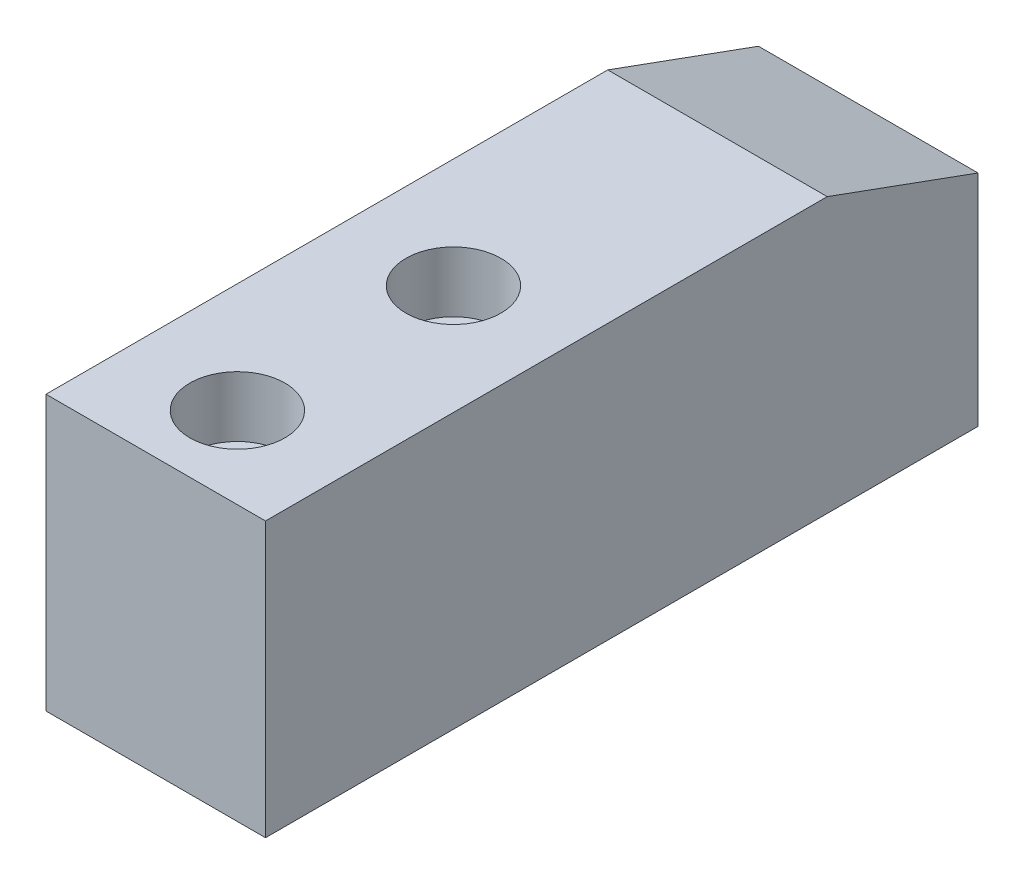
SolidWorks part; units mm, degrees
material "Low Carbon Steel"
ref_plane "Front Plane" through (0, 0, 0) normal (0, 0, 1) x (1, 0, 0)
ref_plane "Top Plane" through (0, 0, 0) normal (0, 1, 0) x (1, 0, 0)
ref_plane "Right Plane" through (0, 0, 0) normal (1, 0, 0) x (0, 0, -1)
sketch "Sketch1" plane through (0, 0, 0) normal (1, 0, 0) x (0, 0, -1)
  line L0 (0, 0) -> (82.4465, 0)
  line L1 (82.4465, 0) -> (82.4465, 25.4)
  line L2 (82.4465, 25.4) -> (65, 31.75)
  line L3 (65, 31.75) -> (0, 31.75)
  line L4 (0, 31.75) -> (0, 0)
  point P4 (70.495, 29.75)
  dimension "D1" = 20
  dimension "D2" = 25.4
  dimension "D3" = 31.75
  dimension "D4" = 65
  dimension "D5" = 2
extrude "Boss-Extrude1" add sketch "Sketch1" along normal mid plane 25.4
hole_wizard "CBORE for M6 Hex Socket Head Cap Screw1" positions "Sketch4" profile "Sketch3" counterbore size "M6" standard "Peddi DIN" end condition through all
sketch "Sketch4" plane through (0, 31.75, 0) normal (0, 1, 0) x (1, 0, 0)
  line L0 (0, 34.4465) -> (0, 9.4465) construction
  line L1 (0, 9.4465) -> (0, 0) construction
  line L2 (12.7, 0) -> (-12.7, 0) construction
  line L4 (12.7, 82.4465) -> (-12.7, 82.4465) construction
  point P0 (0, 9.4465)
  point P2 (0, 34.4465)
  dimension "D1" = 25
  dimension "D2" = 48
sketch "Sketch3" plane through (0, 31.75, -9.4465) normal (1, 0, 0) x (0, 0, 1)
  line L0 (0, 0) -> (0, 31.75)
  line L1 (0, 31.75) -> (3.3, 31.75)
  line L3 (3.3, 31.75) -> (3.3, 7)
  line L4 (3.3, 7) -> (5.5, 7)
  line L5 (5.5, 7) -> (5.5, 0)
  line L7 (5.5, 0) -> (0, 0)
  line L11 (0, -6.35) -> (0, 107.95) construction
  dimension "Thru Hole Dia." = 6.6
  dimension "Thru Hole Depth" = 31.75
  dimension "C'Bore Dia." = 11
  dimension "C'Bore Depth" = 7
ref_axis "Trip point" through (0, 29.75, -70.495) along (1, 0, 0)
other "Freeze***"
